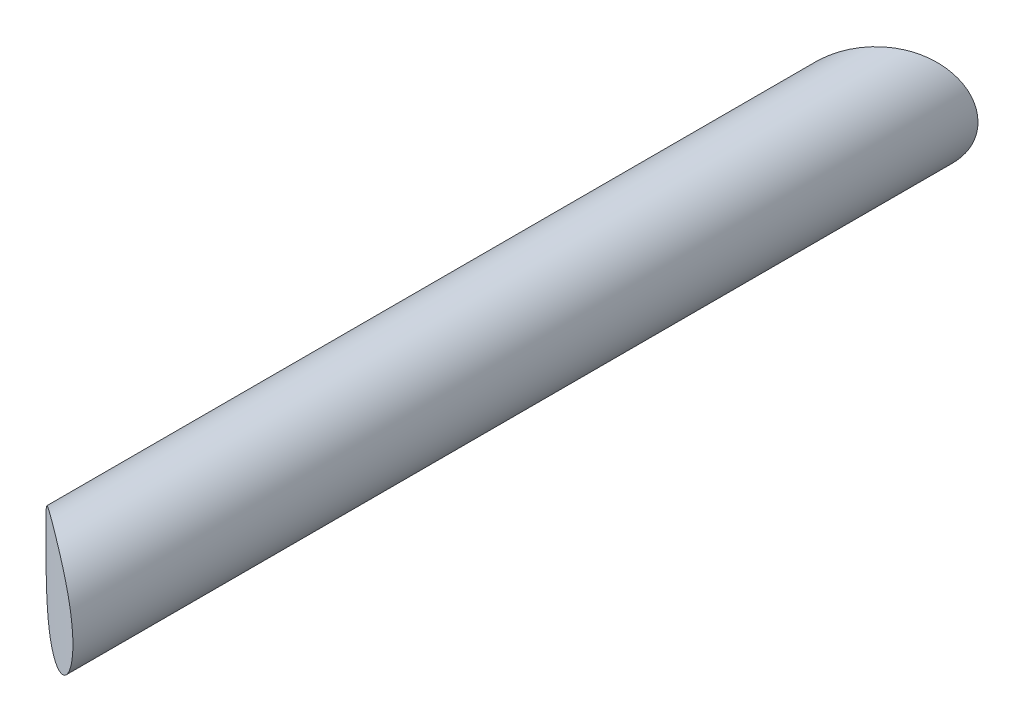
SolidWorks part; units mm, degrees
ref_plane "Front Plane" through (0, 0, 0) normal (0, 0, 1) x (1, 0, 0)
ref_plane "Top Plane" through (0, 0, 0) normal (0, 1, 0) x (1, 0, 0)
ref_plane "Right Plane" through (0, 0, 0) normal (1, 0, 0) x (0, 0, -1)
sketch "Sketch2" plane through (0, 0, 0) normal (0, 0, 1) x (1, 0, 0)
  circle A0 centre (0, 0) radius 1.35
  dimension "D1" = 2.7
extrude "Boss-Extrude1" add sketch "Sketch2" along normal blind 12.7 and the other way blind 12.7
sketch "Sketch3" plane through (0, 0, 0) normal (0, 1, 0) x (1, 0, 0)
  circle A0 centre (7.5946, 0) radius 12.7
  circle A1 centre (7.5946, 0) radius 25.4
  dimension "D2" = 25.4
  dimension "D3" = 50.8
  dimension "D1" = 7.5946
extrude "Cut-Extrude1" cut sketch "Sketch3" against normal through all both and the other way through all contours A1 A0 region at (-17.087, 0, 0)
